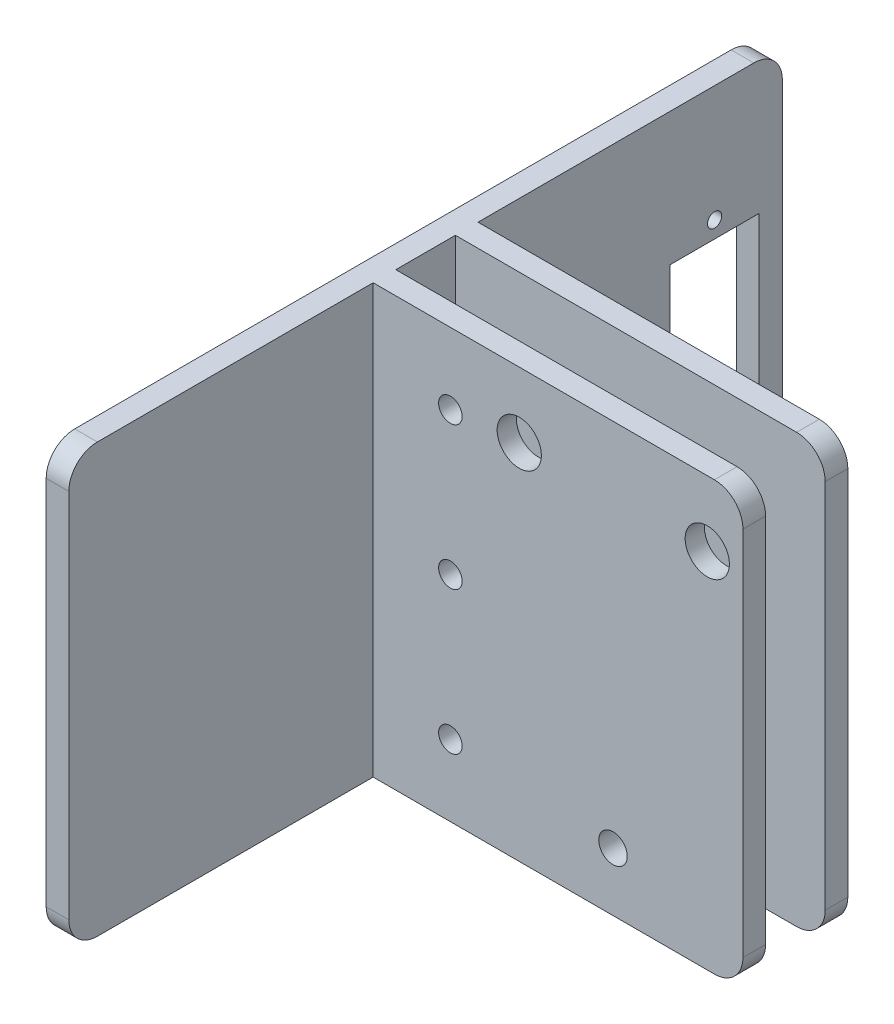
SolidWorks part; units mm, degrees
ref_plane "Front Plane" through (0, 0, 0) normal (0, 0, 1) x (1, 0, 0)
ref_plane "Top Plane" through (0, 0, 0) normal (0, 1, 0) x (1, 0, 0)
ref_plane "Right Plane" through (0, 0, 0) normal (1, 0, 0) x (0, 0, -1)
sketch "Sketch1" plane through (0, 0, 0) normal (0, 1, 0) x (1, 0, 0)
  line L0 (0, 7.35) -> (0, -7.35)
  line L5 (0, -7.35) -> (55, -7.35)
  line L6 (55, -7.35) -> (55, -4.175)
  line L17 (55, -4.175) -> (3.175, -4.175)
  line L18 (3.175, -4.175) -> (3.175, 4.175)
  line L19 (0, 0) -> (39.6882, 0) construction
  line L20 (55, 4.175) -> (3.175, 4.175)
  line L21 (55, 7.35) -> (55, 4.175)
  line L22 (0, 7.35) -> (55, 7.35)
  point P9 (3.175, 0)
  dimension "D1" = 14.7
  dimension "D2" = 3.175
  dimension "D3" = 3.175
  dimension "D4" = 55
extrude "Boss-Extrude1" add sketch "Sketch1" along normal blind 60
sketch "Sketch3" plane through (0, 0, 7.35) normal (0, 0, 1) x (1, 0, 0)
  line L1 (55, 60) -> (55, 0) construction
  line L2 (0, 60) -> (55, 60) construction
  circle A0 centre (50, 50.82) radius 3.1
  circle A1 centre (23.65, 50.82) radius 3.1
  point P8 (0, 0)
  dimension "D1" = 6.2
  dimension "D2" = 9.18
  dimension "D3" = 5
  dimension "D4" = 26.35
extrude "Cut-Extrude1" cut sketch "Sketch3" against normal blind 2.7
sketch "Sketch4" plane through (0, 0, -7.35) normal (0, 0, -1) x (-1, 0, 0)
  line L1 (-55, 60) -> (-55, 0) construction
  line L2 (0, 60) -> (-55, 60) construction
  circle A0 centre (-50, 50.82) radius 3.1
  circle A1 centre (-23.65, 50.82) radius 3.1
  point P4 (0, 0)
  dimension "D4" = 6.2
  dimension "D1" = 9.18
  dimension "D2" = 5
  dimension "D3" = 26.35
extrude "Cut-Extrude2" cut sketch "Sketch4" against normal blind 2.7
fillet "Fillet1" radius 4 4 edges at (55, 60, 5.7625) (55, 60, -5.7625) (55, 0, -5.7625) (55, 0, 5.7625)
sketch "Sketch5" plane through (0, 0, 7.35) normal (0, 0, 1) x (1, 0, 0)
  line L0 (0, 30) -> (55, 30) construction
  line L1 (0, 60) -> (0, 0) construction
  line L2 (55, 56) -> (55, 4) construction
  circle A0 centre (14, 10) radius 1.65
  circle A1 centre (14, 50) radius 1.65
  circle A2 centre (14, 30) radius 1.65
  point P10 (0, 0)
  dimension "D3" = 3.3
  dimension "D1" = 20
  dimension "D2" = 20
  dimension "D4" = 14
extrude "Cut-Extrude3" cut sketch "Sketch5" against normal up to surface (14.7 mm away) up to face at (46.9, 50.82, -7.35)
sketch "Sketch6" plane through (0, 0, 7.35) normal (0, 0, 1) x (1, 0, 0)
  line L0 (0, 0) -> (51, 0) construction
  line L1 (0, 60) -> (3.175, 60)
  line L2 (0, 60) -> (0, 0)
  line L3 (0, 0) -> (3.175, 0)
  line L4 (3.175, 60) -> (3.175, 0)
  dimension "D1" = 3.175
extrude "Boss-Extrude2" add sketch "Sketch6" along normal blind 42.65
sketch "Sketch7" plane through (0, 0, -7.35) normal (0, 0, -1) x (-1, 0, 0)
  line L0 (-51, 60) -> (0, 60) construction
  line L1 (0, 0) -> (-3.175, 0)
  line L2 (0, 0) -> (0, 60)
  line L3 (0, 60) -> (-3.175, 60)
  line L4 (-3.175, 0) -> (-3.175, 60)
  dimension "D1" = 3.175
extrude "Boss-Extrude3" add sketch "Sketch7" along normal blind 42.65
fillet "Fillet2" radius 4 4 edges at (1.5875, 0, -50) (1.5875, 60, -50) (1.5875, 0, 50) (1.5875, 60, 50)
sketch "Sketch8" plane through (0, 0, -4.175) normal (0, 0, 1) x (1, 0, 0)
  line L0 (3.175, 0) -> (51, 0) construction
  line L1 (55, 56) -> (55, 4) construction
  circle A0 centre (36.82, 8.17) radius 2
  point P4 (0, 0)
  dimension "D3" = 4
  dimension "D1" = 8.17
  dimension "D2" = 18.18
extrude "Cut-Extrude5" cut sketch "Sketch8" against normal up to surface (3.175 mm away) up to face at (20.55, 50.82, -7.35)
sketch "Sketch9" plane through (0, 0, 4.175) normal (0, 0, -1) x (-1, 0, 0)
  line L0 (-51, 0) -> (-3.175, 0) construction
  line L1 (-55, 56) -> (-55, 4) construction
  circle A0 centre (-36.79, 8.18) radius 2
  dimension "D1" = 4
  dimension "D2" = 8.18
  dimension "D3" = 18.21
extrude "Cut-Extrude6" cut sketch "Sketch9" against normal up to surface (3.175 mm away) up to face at (26.75, 50.82, 7.35)
sketch "Sketch10" plane through (0, 0, 0) normal (-1, 0, 0) x (0, 0, 1)
  line L0 (-50, 4) -> (-50, 56) construction
  line L3 (-46, 0) -> (46, 0) construction
  line L5 (-34.25, 41.375) -> (-46.75, 41.375)
  line L6 (-34.25, 41.375) -> (-34.25, 18.625)
  line L7 (-34.25, 18.625) -> (-46.75, 18.625)
  line L8 (-46.75, 41.375) -> (-46.75, 18.625)
  circle A0 centre (-40.5, 16.3) radius 1
  circle A1 centre (-40.5, 43.7) radius 1
  dimension "D1" = 2
  dimension "D2" = 27.4
  dimension "D3" = 9.5
  dimension "D4" = 16.3
  dimension "D5" = 12.5
  dimension "D6" = 22.75
  dimension "D7" = 2.325
  dimension "D8" = 6.25
extrude "Cut-Extrude7" cut sketch "Sketch10" against normal up to surface (3.175 mm away) up to face at (3.175, 30, -34.7261)
equation "\"D2@Sketch5\"=\"D1@Sketch5\""
equation "\"D7@Sketch10\"=(\"D2@Sketch10\"-\"D6@Sketch10\")/2"
equation "\"D8@Sketch10\"=\"D5@Sketch10\"/2"
